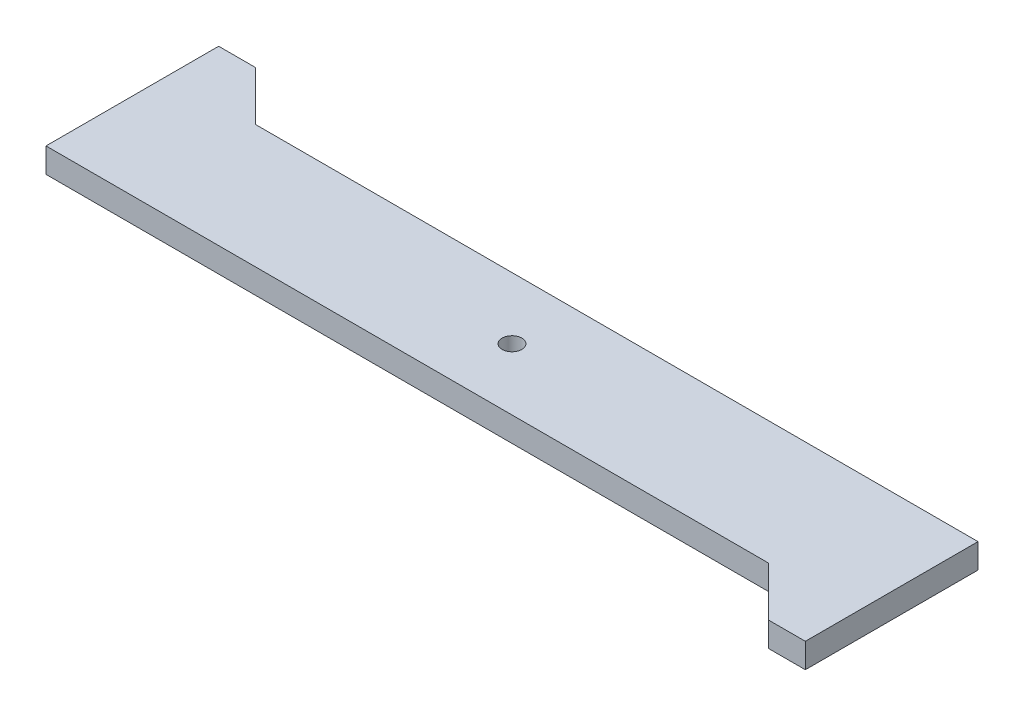
SolidWorks part; units mm, degrees
ref_plane "Front Plane" through (0, 0, 0) normal (0, 0, 1) x (1, 0, 0)
ref_plane "Top Plane" through (0, 0, 0) normal (0, 1, 0) x (1, 0, 0)
ref_plane "Right Plane" through (0, 0, 0) normal (1, 0, 0) x (0, 0, -1)
sketch "Sketch1" plane through (0, 0, 0) normal (0, 1, 0) x (1, 0, 0)
  line L1 (0, 25) -> (-168.1517, 25) construction
  line L2 (-163.936, 25) -> (-163.936, 45) construction
  line L3 (-163.936, 45) -> (-163.936, -25)
  line L8 (-163.936, 45) -> (-148.936, 45)
  line L9 (163.936, -45) -> (148.936, -45)
  line L10 (148.936, -45) -> (148.936, -25) construction
  line L11 (-148.936, 45) -> (-148.936, 25) construction
  line L12 (-163.936, -25) -> (128.936, -25)
  line L13 (128.936, -25) -> (148.936, -45)
  line L14 (163.936, -45) -> (163.936, 25)
  line L15 (163.936, 25) -> (-128.936, 25)
  line L16 (-128.936, 25) -> (-148.936, 45)
  circle A1 centre (0, 0) radius 170 construction
  circle A2 centre (0, 0) radius 4
  point P7 (0, 0)
  point P11 (-128.936, 25)
  point P18 (128.936, -25)
  dimension "D1" = 340
  dimension "D4" = 70
  dimension "D3" = 20
  dimension "D6" = 20
  dimension "D7" = 20
extrude "Boss-Extrude1" add sketch "Sketch1" along normal blind 10
